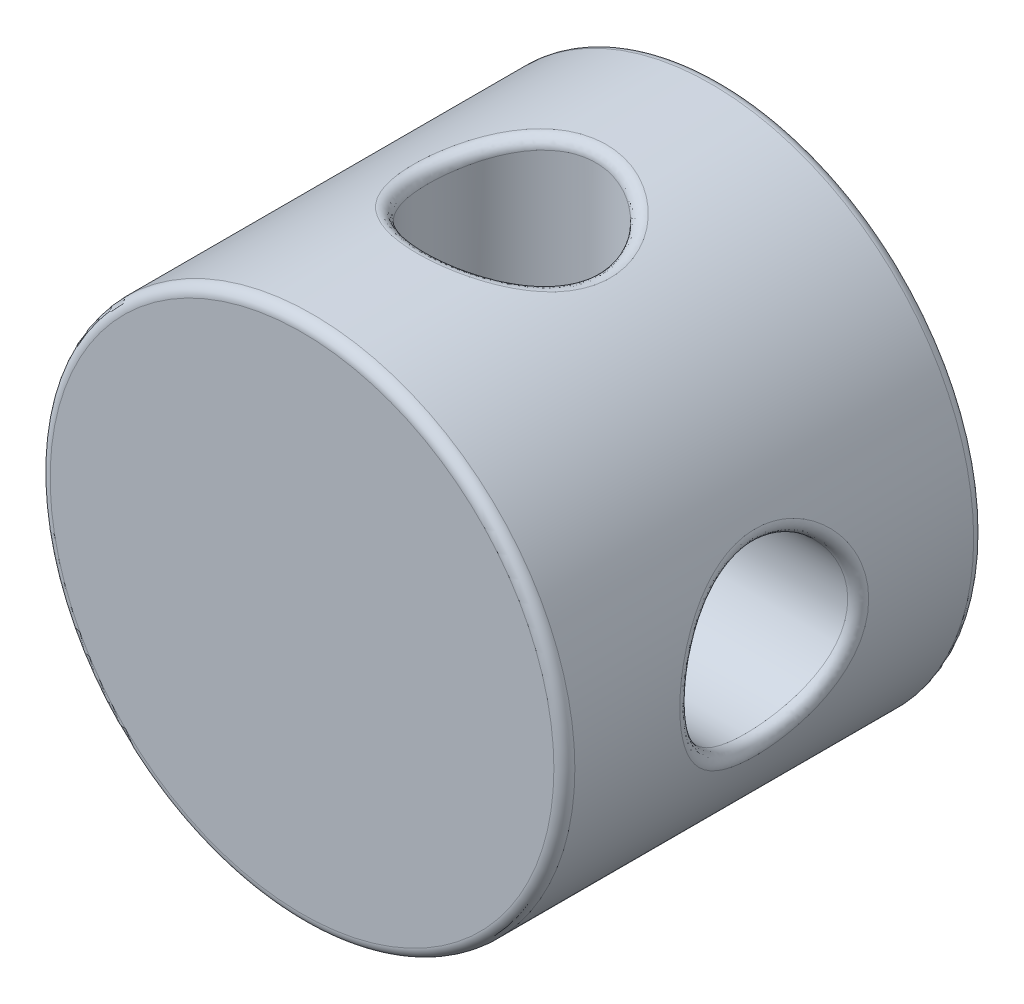
SolidWorks part; units mm, degrees
material "ABS PC"
ref_plane "Front Plane" through (0, 0, 0) normal (0, 0, 1) x (1, 0, 0)
ref_plane "Top Plane" through (0, 0, 0) normal (0, 1, 0) x (1, 0, 0)
ref_plane "Right Plane" through (0, 0, 0) normal (1, 0, 0) x (0, 0, -1)
ref_plane "Plane1" through (0, 0, 150) normal (0, 0, 1) x (1, 0, 0)
sketch "Sketch2" plane through (0, 0, 150) normal (0, 0, 1) x (1, 0, 0)
  line L0 (-75, 200) -> (-75, 100)
  line L1 (-200, 200) -> (200, 200) construction
  line L2 (-200, 200) -> (-200, -200) construction
  line L3 (-200, -200) -> (200, -200) construction
  line L4 (200, 200) -> (200, -200) construction
  line L5 (-200, 200) -> (200, -200) construction
  line L6 (-200, -200) -> (200, 200) construction
  line L7 (35, 200) -> (47.5, 200)
  line L8 (47.5, 200) -> (47.5, 150)
  line L9 (-35, 200) -> (-35, 150)
  line L10 (-35, 150) -> (35, 150)
  line L11 (35, 150) -> (35, 200)
  line L12 (47.5, 150) -> (62.5, 150)
  line L13 (-75, 200) -> (-62.5, 200)
  line L14 (-62.5, 200) -> (-62.5, 150)
  line L15 (-62.5, 150) -> (-47.5, 150)
  line L16 (-47.5, 150) -> (-47.5, 200)
  line L17 (-47.5, 200) -> (-35, 200)
  line L18 (62.5, 150) -> (62.5, 200)
  line L19 (62.5, 200) -> (75, 200)
  line L20 (75, 200) -> (75, 100)
  line L21 (100, 75) -> (200, 75)
  line L22 (200, 75) -> (200, 62.5)
  line L23 (200, 62.5) -> (150, 62.5)
  line L24 (150, 62.5) -> (150, 47.5)
  line L25 (150, 47.5) -> (200, 47.5)
  line L26 (200, 47.5) -> (200, 35)
  line L27 (200, 35) -> (150, 35)
  line L28 (150, 35) -> (150, -35)
  line L29 (150, -35) -> (200, -35)
  line L30 (200, -35) -> (200, -47.5)
  line L31 (200, -47.5) -> (150, -47.5)
  line L32 (150, -47.5) -> (150, -62.5)
  line L33 (150, -62.5) -> (200, -62.5)
  line L34 (200, -62.5) -> (200, -75)
  line L35 (200, -75) -> (100, -75)
  line L36 (100, -75) -> (75, -100)
  line L37 (75, -100) -> (75, -200)
  line L38 (75, -200) -> (62.5, -200)
  line L39 (62.5, -200) -> (62.5, -150)
  line L40 (62.5, -150) -> (47.5, -150)
  line L41 (47.5, -150) -> (47.5, -200)
  line L42 (47.5, -200) -> (35, -200)
  line L43 (35, -200) -> (35, -150)
  line L44 (35, -150) -> (-35, -150)
  line L45 (-35, -150) -> (-35, -200)
  line L46 (-35, -200) -> (-47.5, -200)
  line L47 (-47.5, -200) -> (-47.5, -150)
  line L48 (-47.5, -150) -> (-62.5, -150)
  line L49 (-62.5, -150) -> (-62.5, -200)
  line L50 (-62.5, -200) -> (-75, -200)
  line L51 (-75, -200) -> (-75, -100)
  line L52 (-75, -100) -> (-100, -75)
  line L53 (-100, -75) -> (-200, -75)
  line L54 (-200, -75) -> (-200, -62.5)
  line L55 (-200, -62.5) -> (-150, -62.5)
  line L56 (-150, -62.5) -> (-150, -47.5)
  line L57 (-150, -47.5) -> (-200, -47.5)
  line L58 (-200, -47.5) -> (-200, -35)
  line L59 (-200, -35) -> (-150, -35)
  line L60 (-150, -35) -> (-150, 35)
  line L61 (-150, 35) -> (-200, 35)
  line L62 (-200, 35) -> (-200, 47.5)
  line L63 (-200, 47.5) -> (-150, 47.5)
  line L64 (-150, 47.5) -> (-150, 62.5)
  line L65 (-150, 62.5) -> (-200, 62.5)
  line L66 (-200, 62.5) -> (-200, 75)
  line L67 (-200, 75) -> (-100, 75)
  line L68 (-100, 75) -> (-75, 100)
  line L69 (75, 100) -> (100, 75)
  point P0 (0, 0)
  point P8 (0, 150)
  point P72 (150, 0)
  point P74 (0, -150)
  point P75 (-150, 0)
  dimension "D1" = 400
  dimension "D2" = 400
  dimension "D3" = 12.5
  dimension "D4" = 40
  dimension "D5" = 12.5
  dimension "D6" = 70
  dimension "D7" = 50
  dimension "D8" = 50
  dimension "D9" = 100
  dimension "D10" = 50
  dimension "D11" = 12.5
  dimension "D12" = 12.5
  dimension "D13" = 15
  dimension "D14" = 100
  dimension "D15" = 70
  dimension "D16" = 12.5
  dimension "D17" = 12.5
  dimension "D18" = 15
  dimension "D19" = 12.5
  dimension "D20" = 12.5
  dimension "D21" = 15
  dimension "D22" = 50
  dimension "D23" = 50
  dimension "D24" = 50
  dimension "D25" = 100
  dimension "D26" = 12.5
  dimension "D27" = 12.5
  dimension "D28" = 15
  dimension "D29" = 12.5
  dimension "D30" = 12.5
  dimension "D31" = 15
  dimension "D32" = 70
  dimension "D33" = 100
  dimension "D34" = 100
  dimension "D35" = 12.5
  dimension "D36" = 12.5
  dimension "D37" = 12.5
  dimension "D38" = 12.5
  dimension "D39" = 15
  dimension "D40" = 15
  dimension "D41" = 70
  dimension "D42" = 100
  dimension "D43" = 100
  dimension "D44" = 100
  dimension "D45" = 50
  dimension "D46" = 50
  dimension "D47" = 50
  dimension "D48" = 50
  dimension "D49" = 50
  dimension "D50" = 50
sketch "Sketch20" plane through (0, 0, 150) normal (0, 0, 1) x (1, 0, 0)
  circle A0 centre (200, 200) radius 25
extrude "Boss-Extrude6" add sketch "Sketch20" against normal blind 40 separate body
ref_plane "Plane2" through (0, 210, 0) normal (0, 1, 0) x (1, 0, 0)
sketch "Sketch21" plane through (0, 210, 0) normal (0, 1, 0) x (1, 0, 0)
  line L0 (225, -110) -> (175, -110) construction
  line L1 (225, -150) -> (225, -110) construction
  circle A0 centre (200, -130) radius 8
  dimension "D1" = 20
  dimension "D2" = 25
extrude "Cut-Extrude2" cut sketch "Sketch21" along normal blind 26
ref_axis "Axis1" through (200, 200, 110) along (0, 0, 1)
pattern_circular "CirPattern1" count 2 every 90 about axis through (200, 200, 110) along (0, 0, 1) of "Cut-Extrude2" reverse direction yes
fillet "Fillet5" radius 1 4 edges at (224.961, 201.3957, 137.8773) (198.6043, 224.961, 137.8773) (225, 200, 110) (225, 200, 150)
